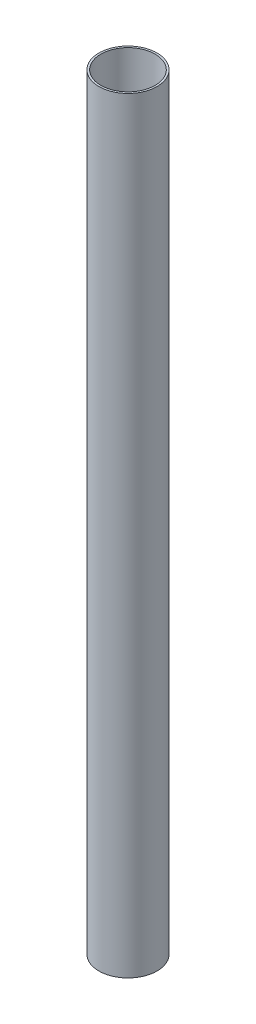
SolidWorks part; units mm, degrees
material "E-Glass Fiber"
ref_plane "Front Plane" through (0, 0, 0) normal (0, 0, 1) x (1, 0, 0)
ref_plane "Top Plane" through (0, 0, 0) normal (0, 1, 0) x (1, 0, 0)
ref_plane "Right Plane" through (0, 0, 0) normal (1, 0, 0) x (0, 0, -1)
sketch "Sketch1" plane through (0, 0, 0) normal (0, 0, 1) x (1, 0, 0)
  line L0 (0, 0) -> (0, -40.98) construction
  line L1 (28.9179, -6.2629) -> (28.9179, -768.2629) construction
  line L2 (26.9875, -6.2629) -> (28.9179, -6.2629)
  line L3 (26.9875, -6.2629) -> (26.9875, -768.2629)
  line L4 (26.9875, -768.2629) -> (28.9179, -768.2629)
  line L5 (28.9179, -6.2629) -> (28.9179, -768.2629)
revolve "Revolve1" add sketch "Sketch1" angle 360 about L0
